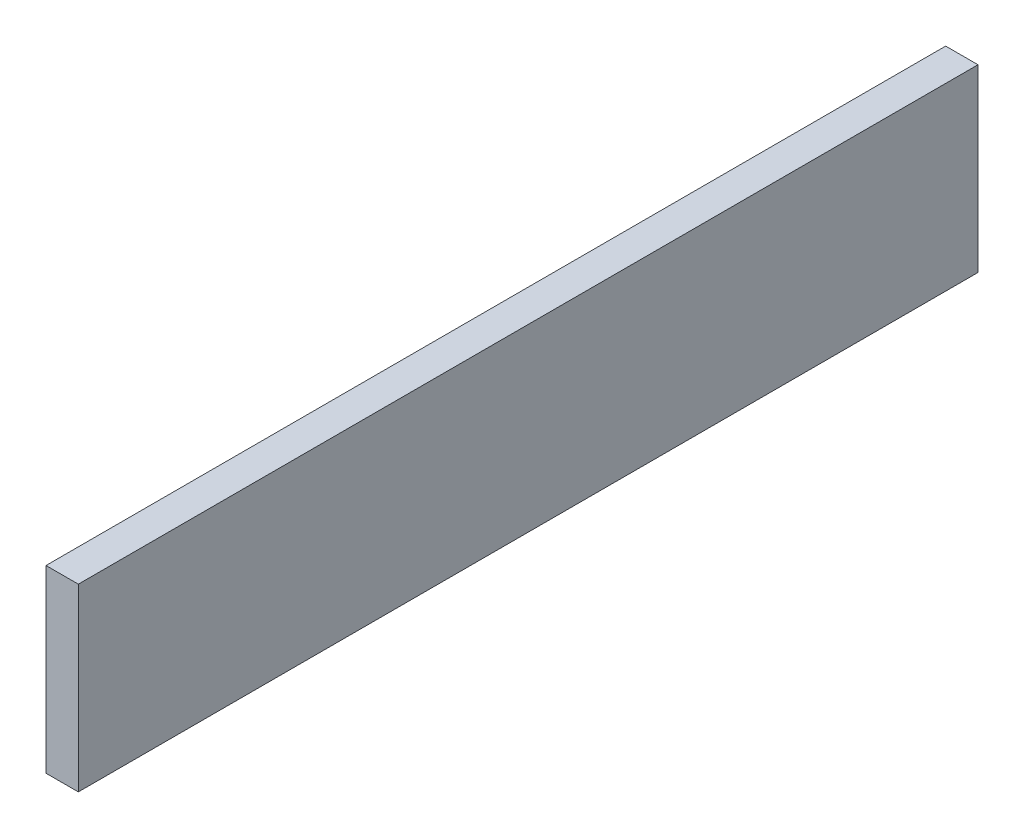
SolidWorks part; units mm, degrees
ref_plane "Front Plane" through (0, 0, 0) normal (0, 0, 1) x (1, 0, 0)
ref_plane "Top Plane" through (0, 0, 0) normal (0, 1, 0) x (1, 0, 0)
ref_plane "Right Plane" through (0, 0, 0) normal (1, 0, 0) x (0, 0, -1)
sketch "Sketch2" plane through (0, 0, 0) normal (0, 0, 1) x (1, 0, 0)
  line L1 (0, 0) -> (18.2563, 0)
  line L2 (0, 0) -> (0, 101.6)
  line L3 (0, 101.6) -> (18.2562, 101.6)
  line L4 (18.2563, 0) -> (18.2562, 101.6)
  dimension "D1" = 101.6
  dimension "D2" = 18.2562
extrude "Boss-Extrude1" add sketch "Sketch2" along normal blind 508
